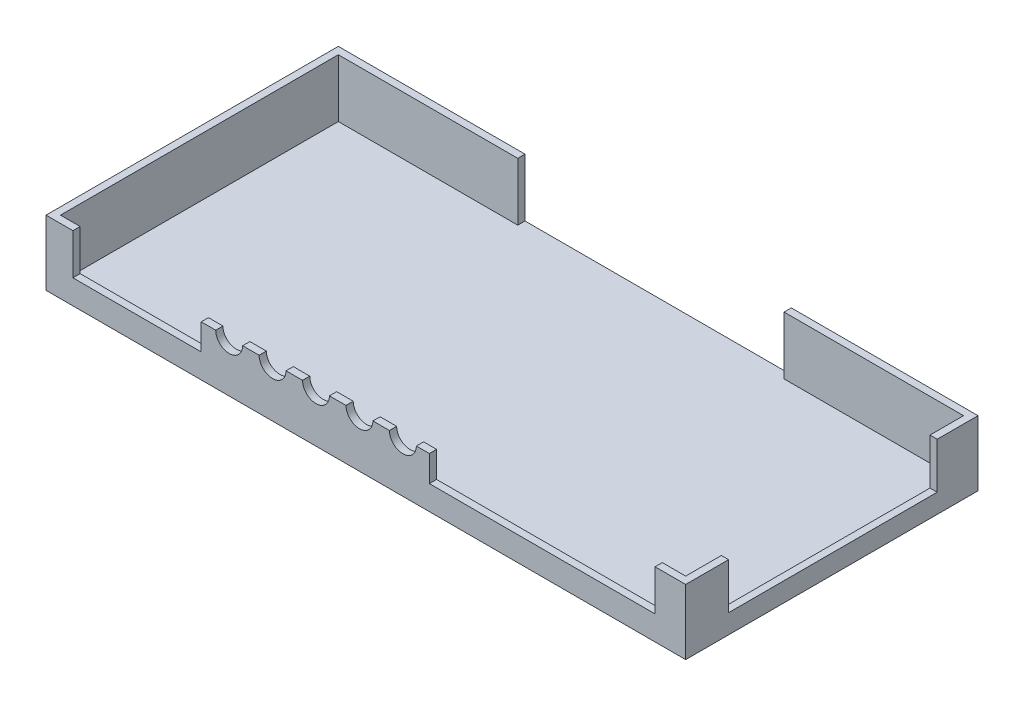
SolidWorks part; units mm, degrees
ref_plane "Front Plane" through (0, 0, 0) normal (0, 0, 1) x (1, 0, 0)
ref_plane "Top Plane" through (0, 0, 0) normal (0, 1, 0) x (1, 0, 0)
ref_plane "Right Plane" through (0, 0, 0) normal (1, 0, 0) x (0, 0, -1)
sketch "Sketch1" plane through (0, 0, 0) normal (0, 1, 0) x (1, 0, 0)
  line L0 (-110.5, -50.5) -> (-110.5, 50.5)
  line L1 (-108, -48) -> (108, -48)
  line L2 (-108, -48) -> (-108, 48)
  line L3 (-108, 48) -> (108, 48)
  line L4 (108, -48) -> (108, 48)
  line L5 (-108, -48) -> (108, 48) construction
  line L6 (-108, 48) -> (108, -48) construction
  line L7 (-110.5, 50.5) -> (110.5, 50.5)
  line L8 (110.5, -50.5) -> (110.5, 50.5)
  line L9 (-110.5, -50.5) -> (110.5, -50.5)
  point P0 (0, 0)
  dimension "D1" = 216
  dimension "D2" = 96
  dimension "D3" = 2.5
extrude "Boss-Extrude1" add sketch "Sketch1" along normal blind 20 contours L0 L9 L8 L7 L4 L1 L2 L3 region at (-108.0701, 0, 0)
extrude "Boss-Extrude2" add sketch "Sketch1<3>" against normal blind 2.5 contours L0 L7 L8 L9
sketch "Sketch1<3>" plane through (0, 0, 0) normal (0, 1, 0) x (1, 0, 0) same geometry as "Sketch1"
ref_plane "Plane1" through (-110.5, 20, 50.5) normal (1, 0, 0) x (0, 0, -1)
sketch "Sketch3" plane through (0, 0, 50.5) normal (0, 0, 1) x (1, 0, 0)
  line L0 (-110.5, 20) -> (110.5, 20) construction
  line L1 (-101.2008, 20) -> (99.9204, 20)
  line L2 (-101.2008, 20) -> (-101.2008, 5.8947)
  line L3 (-101.2008, 5.8947) -> (99.9204, 5.8947)
  line L4 (99.9204, 20) -> (99.9204, 5.8947)
extrude "Cut-Extrude1" cut sketch "Sketch3" against normal blind 10
sketch "Sketch4" plane through (110.5, 0, 0) normal (1, 0, 0) x (0, 0, -1)
  line L0 (-50.5, 20) -> (50.5, 20) construction
  line L1 (-35.6625, 20) -> (36.407, 20)
  line L2 (-35.6625, 20) -> (-35.6625, 4.1415)
  line L3 (-35.6625, 4.1415) -> (36.407, 4.1415)
  line L4 (36.407, 20) -> (36.407, 4.1415)
extrude "Cut-Extrude2" cut sketch "Sketch4" against normal blind 10
sketch "Sketch5" plane through (0, 0, 50.5) normal (0, 0, 1) x (1, 0, 0)
  line L0 (-144.165, 14.8947) -> (142.8743, 14.8947) construction
  line L1 (-101.2008, 5.8947) -> (99.9204, 5.8947) construction
  line L2 (0, -12.375) -> (0, 12.375) construction
  line L4 (-56.87, 5.8947) -> (21.95, 5.8947)
  line L6 (-42.57, 14.8947) -> (-36.87, 14.8947)
  line L7 (-27.57, 14.8947) -> (-21.87, 14.8947)
  line L8 (-12.57, 14.8947) -> (-6.86, 14.8947)
  line L9 (2.44, 14.8947) -> (8.15, 14.8947)
  line L10 (-56.87, 14.8947) -> (-56.87, 5.8947)
  line L11 (-56.87, 14.8947) -> (-51.87, 14.8947)
  line L12 (21.95, 14.8947) -> (21.95, 5.8947)
  line L13 (17.45, 14.8947) -> (21.95, 14.8947)
  circle A0 centre (-47.22, 14.8947) radius 4.65 construction
  circle A1 centre (-32.22, 14.8947) radius 4.65 construction
  circle A2 centre (-17.22, 14.8947) radius 4.65 construction
  circle A3 centre (-2.21, 14.8947) radius 4.65 construction
  circle A4 centre (12.8, 14.8947) radius 4.65 construction
  arc A5 (-51.87, 14.8947) -> (-42.57, 14.8947) centre (-47.22, 14.8947) ccw
  arc A6 (-36.87, 14.8947) -> (-27.57, 14.8947) centre (-32.22, 14.8947) ccw
  arc A7 (-21.87, 14.8947) -> (-12.57, 14.8947) centre (-17.22, 14.8947) ccw
  arc A8 (-6.86, 14.8947) -> (2.44, 14.8947) centre (-2.21, 14.8947) ccw
  arc A9 (8.15, 14.8947) -> (17.45, 14.8947) centre (12.8, 14.8947) ccw
  point P4 (-47.22, 14.8947)
  point P5 (-32.22, 14.8947)
  point P6 (-17.22, 14.8947)
  point P7 (-2.21, 14.8947)
  point P8 (12.8, 14.8947)
  dimension "D7" = 9.3
  dimension "D8" = 5
  dimension "D9" = 4.5
  dimension "D1" = 9
  dimension "D2" = 47.22
  dimension "D3" = 32.22
  dimension "D4" = 17.22
  dimension "D5" = 2.21
  dimension "D6" = 12.8
extrude "Boss-Extrude3" add sketch "Sketch5" against normal up to surface (2.5 mm away) up to face at (-0.3201, 11.4737, 48)
sketch "Sketch6" plane through (0, 0, -50.5) normal (0, 0, -1) x (-1, 0, 0)
  line L0 (110.5, 20) -> (-110.5, 20) construction
  line L1 (-46, 20) -> (46, 20)
  line L2 (-46, 20) -> (-46, 0)
  line L3 (-46, 0) -> (46, 0)
  line L4 (46, 20) -> (46, 0)
  line L5 (0, 12.375) -> (0, -12.375) construction
  dimension "D1" = 92
  dimension "D2" = 46
  dimension "D3" = 20
extrude "Cut-Extrude3" cut sketch "Sketch6" against normal blind 10
equation "\"D2@Sketch6\"=\"D1@Sketch6\"/2"
